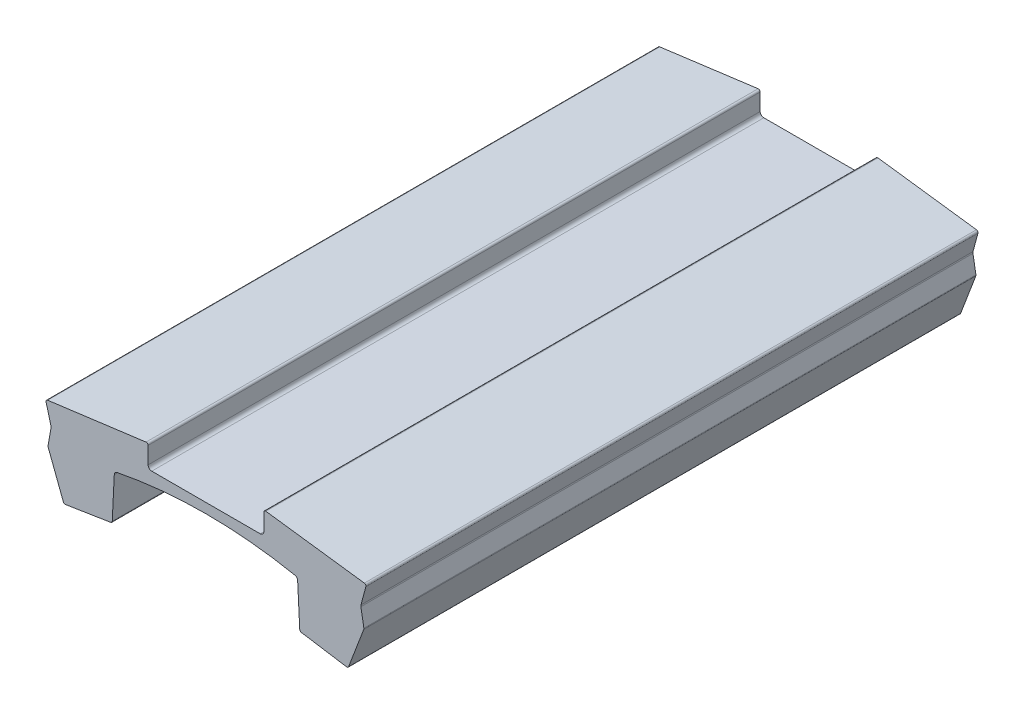
SolidWorks part; units mm, degrees
ref_plane "Ön Düzlem" through (0, 0, 0) normal (0, 0, 1) x (1, 0, 0)
ref_plane "Üst Düzlem" through (0, 0, 0) normal (0, 1, 0) x (1, 0, 0)
ref_plane "Sağ Düzlem" through (0, 0, 0) normal (1, 0, 0) x (0, 0, -1)
sketch "Sketch1" plane through (0, 0, 0) normal (0, 0, 1) x (1, 0, 0)
  line L209 (-17.6248, 90.5561) -> (-17.082, 88.5301)
  line L220 (-17.4061, 86.4651) -> (-17.0743, 88.3575)
  line L221 (-17.396, 86.3593) -> (-15.7146, 81.9531)
  line L222 (-15.4964, 81.8269) -> (-10.4958, 82.6189)
  line L223 (-10.3274, 82.8065) -> (-10.1019, 87.3646)
  line L224 (10.3511, 82.8056) -> (10.1212, 87.365)
  line L225 (15.5201, 81.8261) -> (10.5196, 82.6181)
  line L226 (17.4151, 86.3593) -> (15.7384, 81.9525)
  line L227 (17.0934, 88.3575) -> (17.4252, 86.4649)
  line L228 (17.6439, 90.5561) -> (17.101, 88.5301)
  line L229 (6.6156, 92.2361) -> (17.4768, 90.8062)
  line L231 (6.3895, 92.0378) -> (6.3895, 90.1739)
  line L232 (-5.9705, 89.7739) -> (5.9895, 89.7739)
  line L233 (-6.3705, 92.0378) -> (-6.3705, 90.1739)
  line L234 (-17.4578, 90.8062) -> (-6.5966, 92.2361)
  arc A74 (-17.082, 88.5301) -> (-17.0743, 88.3575) centre (-17.4683, 88.4265) cw
  arc A75 (-17.396, 86.3593) -> (-17.4061, 86.4651) centre (-17.2091, 86.4306) cw
  arc A93 (-15.7146, 81.9531) -> (-15.4964, 81.8269) centre (-15.5277, 82.0244) ccw
  arc A94 (-10.4958, 82.6189) -> (-10.3274, 82.8065) centre (-10.5271, 82.8164) ccw
  arc A95 (-9.7798, 87.7373) -> (-10.1019, 87.3646) centre (-9.7024, 87.3449) ccw
  arc A96 (-9.7798, 87.7373) -> (9.7991, 87.7373) centre (0.0095, 38.0933) cw
  arc A97 (10.1212, 87.365) -> (9.7991, 87.7373) centre (9.7217, 87.3448) ccw
  arc A98 (10.3511, 82.8056) -> (10.5196, 82.6181) centre (10.5509, 82.8157) ccw
  arc A99 (15.5201, 81.8261) -> (15.7384, 81.9525) centre (15.5514, 82.0237) ccw
  arc A100 (17.4151, 86.3593) -> (17.4252, 86.4649) centre (17.2282, 86.4304) ccw
  arc A101 (17.101, 88.5301) -> (17.0934, 88.3575) centre (17.4874, 88.4265) ccw
  arc A102 (17.4768, 90.8062) -> (17.6439, 90.5561) centre (17.4507, 90.6079) cw
  arc A103 (6.6156, 92.2361) -> (6.3895, 92.0378) centre (6.5895, 92.0378) ccw
  arc A104 (6.3895, 90.1739) -> (5.9895, 89.7739) centre (5.9895, 90.1739) cw
  arc A105 (-5.9705, 89.7739) -> (-6.3705, 90.1739) centre (-5.9705, 90.1739) cw
  arc A106 (-6.3705, 92.0378) -> (-6.5966, 92.2361) centre (-6.5705, 92.0378) ccw
  arc A107 (-17.4578, 90.8062) -> (-17.6248, 90.5561) centre (-17.4317, 90.6079) ccw
  point P0 (0, 0)
  point P7 (0, 0)
extrude "Boss-Extrude2" add sketch "Sketch1" along normal blind 67.5 contours L209 A74 L220 A75 L221 A93 L222 A94 L223 A95 A96 A97 L224 A98 L225 A99 L226 A100 L227 A101 L228 A102 L229 A103 L231 A104 L232 A105 L233 A106 L234 A107
